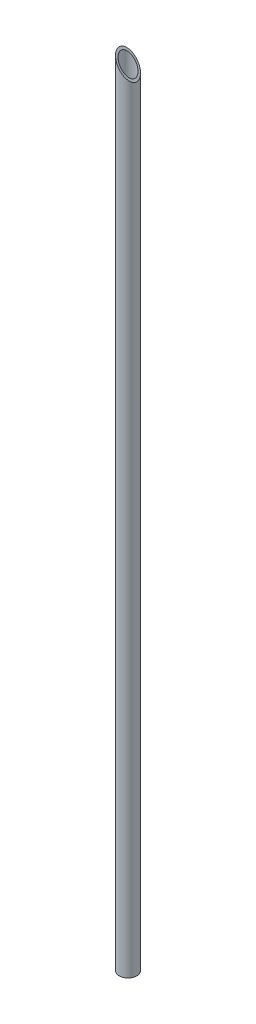
SolidWorks part; units mm, degrees
material "Nickel"
ref_plane "Front Plane" through (0, 0, 0) normal (0, 0, 1) x (1, 0, 0)
ref_plane "Top Plane" through (0, 0, 0) normal (0, 1, 0) x (1, 0, 0)
ref_plane "Right Plane" through (0, 0, 0) normal (1, 0, 0) x (0, 0, -1)
sketch "Sketch1" plane through (0, 0, 0) normal (0, 1, 0) x (1, 0, 0)
  circle A0 centre (0, 0) radius 0.5
  dimension "D1" = 1
extrude "Extrude1" add sketch "Sketch1" along normal blind 45
shell "Shell1" thickness 0.1 removed face at (0, 0, 0.5) removed face at (0, 45, 0.5)
sketch "Sketch2" plane through (0, 0, 0) normal (0, 0, 1) x (1, 0, 0)
  line L0 (-0.5, 45) -> (3.9668, 39.5573)
  line L1 (3.9668, 39.5573) -> (3.9668, 46.046)
  line L2 (3.9668, 46.046) -> (-0.5, 45)
extrude "Cut-Extrude1" cut sketch "Sketch2" against normal blind 45 and the other way blind 45
